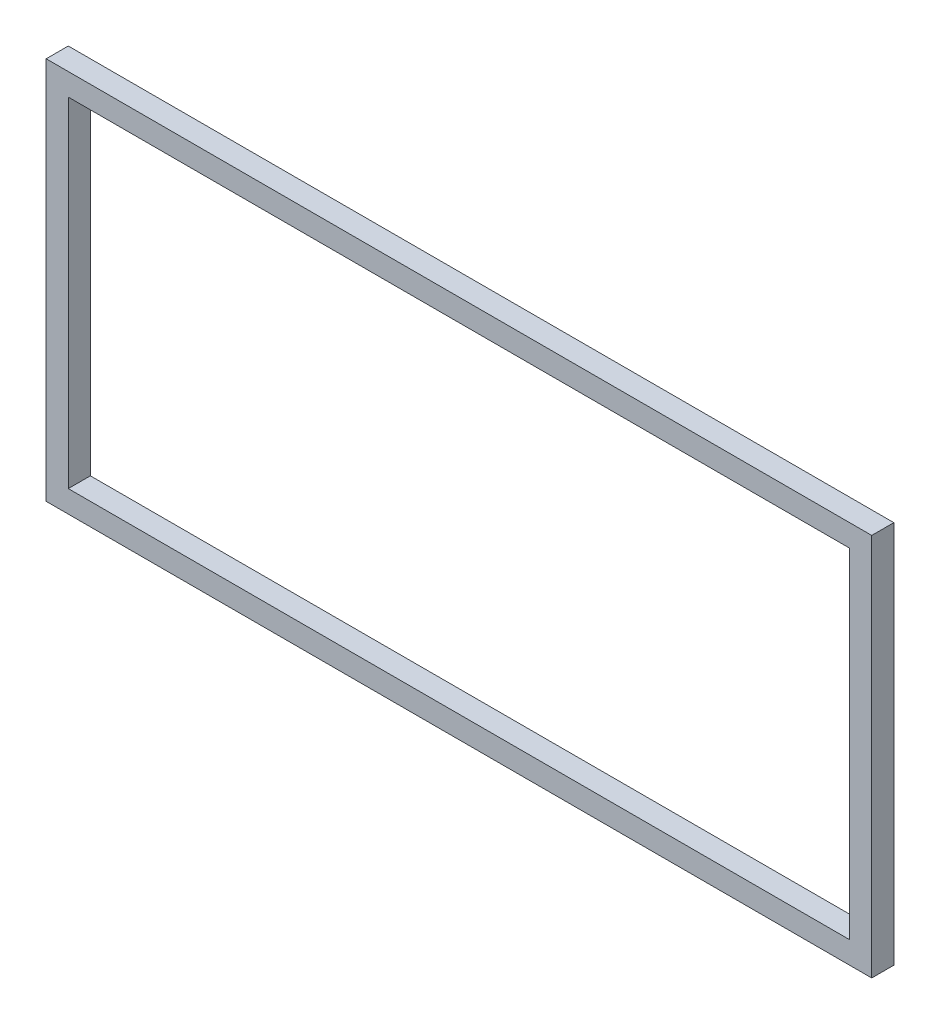
SolidWorks part; units mm, degrees
ref_plane "前视基准面" through (0, 0, 0) normal (0, 0, 1) x (1, 0, 0)
ref_plane "上视基准面" through (0, 0, 0) normal (0, 1, 0) x (1, 0, 0)
ref_plane "右视基准面" through (0, 0, 0) normal (1, 0, 0) x (0, 0, -1)
other "Configuration Table"
sketch "Sketch1" plane through (0, 0, 0) normal (0, 0, 1) x (1, 0, 0)
  line L1 (-560, -260) -> (560, -260)
  line L2 (-560, -260) -> (-560, 260)
  line L3 (-560, 260) -> (560, 260)
  line L4 (560, -260) -> (560, 260)
  line L5 (-560, -260) -> (560, 260) construction
  line L6 (-560, 260) -> (560, -260) construction
  line L7 (-530, -230) -> (530, -230)
  line L8 (-530, -230) -> (-530, 230)
  line L9 (-530, 230) -> (530, 230)
  line L10 (530, -230) -> (530, 230)
  line L11 (-530, -230) -> (530, 230) construction
  line L12 (-530, 230) -> (530, -230) construction
  point P0 (0, 0)
  point P6 (0, 0)
extrude "Boss-Extrude1" add sketch "Sketch1" along normal blind 30
ref_plane "end_face_y_minus" through (0, -260, 0) normal (0, 1, 0) x (1, 0, 0)
ref_plane "end_face_y_plus" through (0, 260, 0) normal (0, 1, 0) x (1, 0, 0)
sketch3d "3DSketch1"
  line L0 (-560, 0, 15) -> (560, 0, 15) construction
ref_axis "axis_x_center" through (-560, 0, 15) along (1, 0, 0)
sketch3d "3DSketch2"
  line L0 (0, -260, 15) -> (0, 260, 15) construction
ref_axis "axis_y_center" through (0, -260, 15) along (0, 1, 0)
